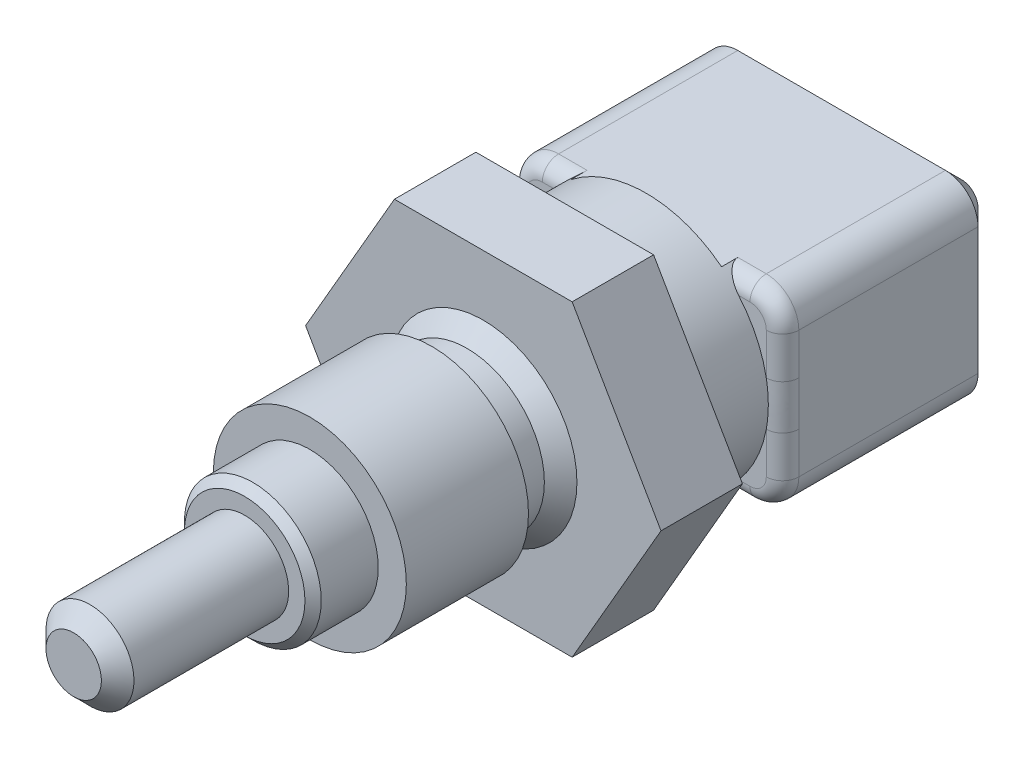
SolidWorks part; units mm, degrees
ref_plane "Front Plane" through (0, 0, 0) normal (0, 0, 1) x (1, 0, 0)
ref_plane "Top Plane" through (0, 0, 0) normal (0, 1, 0) x (1, 0, 0)
ref_plane "Right Plane" through (0, 0, 0) normal (1, 0, 0) x (0, 0, -1)
sketch "Sketch1" plane through (0, 0, 0) normal (0, 0, 1) x (1, 0, 0)
  line L0 (0, 23.3833) -> (0, -23.3833) construction
  line L1 (-5.456, 9.45) -> (-10.9119, 0)
  line L2 (-10.9119, 0) -> (-5.456, -9.45)
  line L3 (-5.456, -9.45) -> (5.456, -9.45)
  line L4 (5.456, -9.45) -> (10.9119, 0)
  line L5 (10.9119, 0) -> (5.456, 9.45)
  line L6 (5.456, 9.45) -> (-5.456, 9.45)
  circle A0 centre (0, 0) radius 9.45 construction
  dimension "D1" = 18.9
extrude "Extrude1" add sketch "Sketch1" along normal blind 5
sketch "Sketch2" plane through (0, 0, 5) normal (0, 0, 1) x (1, 0, 0)
  circle A0 centre (0, 0) radius 4.75
  dimension "D1" = 9.5
extrude "Extrude2" add sketch "Sketch2" along normal blind 3.15
chamfer "Chamfer1" distance 1 angle 45 1 edges at (4.75, 0, 5)
sketch "Sketch3" plane through (0, 0, 8.15) normal (0, 0, 1) x (1, 0, 0)
  circle A0 centre (0, 0) radius 5.925
  dimension "D1" = 11.85
extrude "Extrude3" add sketch "Sketch3" along normal blind 7.5
sketch "Sketch4" plane through (0, 0, 15.65) normal (0, 0, 1) x (1, 0, 0)
  circle A0 centre (0, 0) radius 4.2
  dimension "D1" = 8.4
extrude "Extrude4" add sketch "Sketch4" along normal blind 4
chamfer "Chamfer2" distance 0.5 angle 45 1 edges at (4.2, 0, 19.65)
sketch "Sketch5" plane through (0, 0, 19.65) normal (0, 0, 1) x (1, 0, 0)
  circle A0 centre (0, 0) radius 2.7
  dimension "D1" = 5.4
extrude "Extrude5" add sketch "Sketch5" along normal blind 10.5
chamfer "Chamfer3" distance 1 angle 45 1 edges at (2.7, 0, 30.15)
sketch "Sketch6" plane through (0, 0, 0) normal (0, 0, -1) x (-1, 0, 0)
  circle A0 centre (0, 0) radius 7.5
  dimension "D1" = 15
extrude "Extrude6" add sketch "Sketch6" along normal blind 5
sketch "Sketch7" plane through (0, 0, -5) normal (0, 0, -1) x (-1, 0, 0)
  line L0 (0, 11.8253) -> (0, -11.5236) construction
  line L1 (-6.375, 5.9) -> (6.375, 5.9)
  line L2 (-8.375, 3.9) -> (-8.375, -3.9)
  line L3 (-6.375, -5.9) -> (6.375, -5.9)
  line L4 (8.375, 3.9) -> (8.375, -3.9)
  line L5 (-16.9234, 0) -> (17.6229, 0) construction
  arc A0 (-8.375, 3.9) -> (-6.375, 5.9) centre (-6.375, 3.9) cw
  arc A1 (-6.375, -5.9) -> (-8.375, -3.9) centre (-6.375, -3.9) cw
  arc A2 (8.375, -3.9) -> (6.375, -5.9) centre (6.375, -3.9) cw
  arc A3 (6.375, 5.9) -> (8.375, 3.9) centre (6.375, 3.9) cw
  dimension "D3" = 2
  dimension "D1" = 11.8
  dimension "D2" = 16.75
extrude "Extrude7" add sketch "Sketch7" along normal blind 13
fillet "Fillet1" radius 1 10 edges at (-5.5027, -5.9, -5) (-7.7892, -5.3142, -5) (-5.5027, 5.9, -5) (-7.7892, 5.3142, -5) (5.5027, 5.9, -5) (7.7892, 5.3142, -5) (5.5027, -5.9, -5) (7.7892, -5.3142, -5) (-8.375, 0, -5) (8.375, 0, -5)
chamfer "Chamfer4" distance 1 angle 45 8 edges at (-7.7892, 5.3142, -18) (-8.375, 0, -18) (-7.7892, -5.3142, -18) (0, -5.9, -18) (7.7892, -5.3142, -18) (8.375, 0, -18) (7.7892, 5.3142, -18) (0, 5.9, -18)
sketch "Sketch8" plane through (0, 0, -18) normal (0, 0, -1) x (-1, 0, 0)
  line L12 (7.125, -3.9) -> (7.125, 3.9)
  line L13 (6.375, 4.65) -> (-6.375, 4.65)
  line L14 (-7.125, 3.9) -> (-7.125, -3.9)
  line L15 (-6.375, -4.65) -> (6.375, -4.65)
  line L16 (7.125, -3.9) -> (7.125, 3.9)
  line L17 (6.375, 4.65) -> (-6.375, 4.65)
  line L18 (-7.125, 3.9) -> (-7.125, -3.9)
  line L19 (-6.375, -4.65) -> (6.375, -4.65)
  arc A12 (7.125, 3.9) -> (6.375, 4.65) centre (6.375, 3.9) ccw
  arc A13 (-6.375, 4.65) -> (-7.125, 3.9) centre (-6.375, 3.9) ccw
  arc A14 (-7.125, -3.9) -> (-6.375, -4.65) centre (-6.375, -3.9) ccw
  arc A15 (6.375, -4.65) -> (7.125, -3.9) centre (6.375, -3.9) ccw
  arc A16 (7.125, 3.9) -> (6.375, 4.65) centre (6.375, 3.9) ccw
  arc A17 (-6.375, 4.65) -> (-7.125, 3.9) centre (-6.375, 3.9) ccw
  arc A18 (-7.125, -3.9) -> (-6.375, -4.65) centre (-6.375, -3.9) ccw
  arc A19 (6.375, -4.65) -> (7.125, -3.9) centre (6.375, -3.9) ccw
  dimension "D1" = 0.25
extrude "Cut-Extrude1" cut sketch "Sketch8" against normal blind 5
